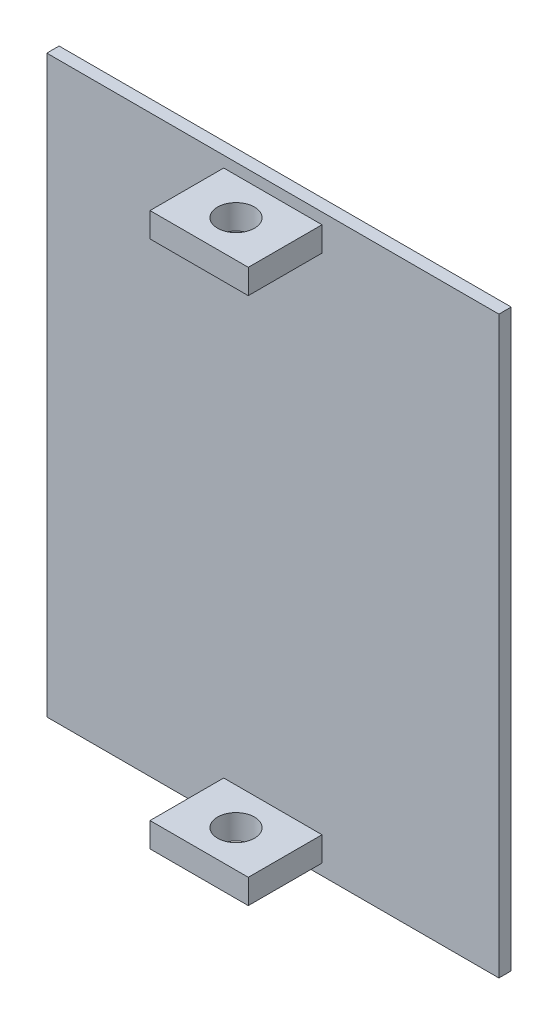
SolidWorks part; units mm, degrees
ref_plane "Alzado" through (0, 0, 0) normal (0, 0, 1) x (1, 0, 0)
ref_plane "Planta" through (0, 0, 0) normal (0, 1, 0) x (1, 0, 0)
ref_plane "Vista lateral" through (0, 0, 0) normal (1, 0, 0) x (0, 0, -1)
sketch "Croquis1" plane through (0, 0, 0) normal (0, 0, 1) x (1, 0, 0)
  line L1 (-18.4, -23.4) -> (18.4, -23.4)
  line L2 (-18.4, -23.4) -> (-18.4, 23.4)
  line L3 (-18.4, 23.4) -> (18.4, 23.4)
  line L4 (18.4, -23.4) -> (18.4, 23.4)
  line L5 (-18.4, -23.4) -> (18.4, 23.4) construction
  line L6 (-18.4, 23.4) -> (18.4, -23.4) construction
  point P0 (0, 0)
  dimension "D1" = 46.8
  dimension "D2" = 36.8
extrude "Saliente-Extruir1" add sketch "Croquis1" along normal blind 1
sketch "Croquis2" plane through (0, 0, 0) normal (0, 0, 1) x (1, 0, 0)
  line L0 (0, 0) -> (0, 22.5) construction
  line L1 (-17.5, -22.5) -> (17.5, -22.5)
  line L2 (-17.5, -22.5) -> (-17.5, 22.5)
  line L3 (-17.5, 22.5) -> (17.5, 22.5)
  line L4 (17.5, -22.5) -> (17.5, 22.5)
  line L5 (-17.5, -22.5) -> (17.5, 22.5) construction
  line L6 (-17.5, 22.5) -> (17.5, -22.5) construction
  line L7 (0, 0) -> (0, -22.5) construction
  line L9 (-4, 20.5) -> (4, 20.5)
  line L10 (-4, 20.5) -> (-4, 22.5)
  line L11 (-4, 22.5) -> (4, 22.5)
  line L12 (4, 20.5) -> (4, 22.5)
  line L13 (-4, 20.5) -> (4, 22.5) construction
  line L14 (-4, 22.5) -> (4, 20.5) construction
  line L15 (-4, -20.5) -> (4, -20.5)
  line L16 (-4, -20.5) -> (-4, -22.5)
  line L17 (-4, -22.5) -> (4, -22.5)
  line L18 (4, -20.5) -> (4, -22.5)
  line L19 (-4, -20.5) -> (4, -22.5) construction
  line L20 (-4, -22.5) -> (4, -20.5) construction
  point P0 (0, 0)
  point P8 (0, 21.5)
  point P14 (0, -21.5)
  dimension "D1" = 35
  dimension "D2" = 45
  dimension "D3" = 2
  dimension "D4" = 8
  dimension "D5" = 2
  dimension "D6" = 8
extrude "Saliente-Extruir2" add sketch "Croquis2" along normal blind 7 contours L12 L11 L10 L9
extrude "Saliente-Extruir3" add sketch "Croquis2<3>" along normal blind 7 contours L18 L17 L16 L15
sketch "Croquis2<3>" plane through (0, 0, 0) normal (0, 0, 1) x (1, 0, 0) same geometry as "Croquis2"
sketch "Croquis6" plane through (0, 22.5, 0) normal (0, 1, 0) x (1, 0, 0)
  line L0 (-4, -1) -> (4, -7) construction
  circle A0 centre (0, -4) radius 1.5
extrude "Cortar-Extruir1" cut sketch "Croquis6" against normal through all
